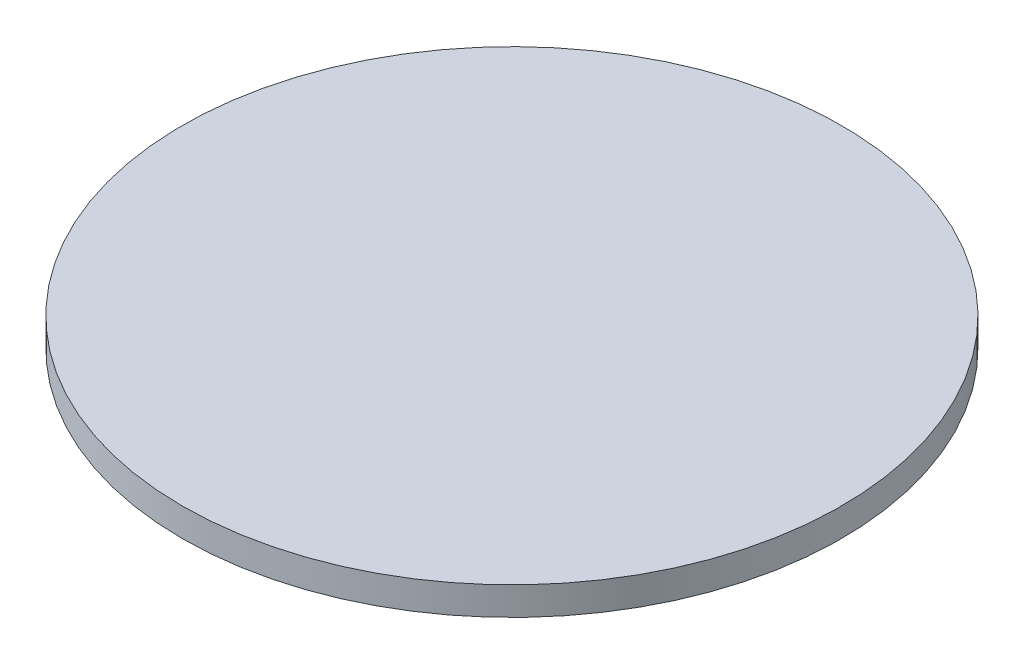
SolidWorks part; units mm, degrees
material "ABS"
ref_plane "Front Plane" through (0, 0, 0) normal (0, 0, 1) x (1, 0, 0)
ref_plane "Top Plane" through (0, 0, 0) normal (0, 1, 0) x (1, 0, 0)
ref_plane "Right Plane" through (0, 0, 0) normal (1, 0, 0) x (0, 0, -1)
sketch "Sketch1" plane through (0, 0, 0) normal (0, 1, 0) x (1, 0, 0)
  circle A0 centre (0, 0) radius 1.55
  dimension "D1" = 3.1
sketch "Sketch3" plane through (0, 0, 0) normal (0, 0, 1) x (1, 0, 0)
  line L0 (0, 0) -> (2.5, 0)
  line L1 (0, 0) -> (0, 5)
  line L2 (0, 5) -> (5, 5)
  line L3 (2.5, 0) -> (5, 5)
  dimension "D1" = 2.5
  dimension "D2" = 5
  dimension "D3" = 5
revolve "Revolve1" add sketch "Sketch3" angle 360 about L1
sketch "Sketch5" plane through (0, 5, 0) normal (0, 1, 0) x (1, 0, 0)
  circle A0 centre (0, 0) radius 5
extrude "Boss-Extrude2" add sketch "Sketch5" along normal blind 5
sketch "Sketch6" plane through (0, 10, 0) normal (0, 1, 0) x (1, 0, 0)
  circle A0 centre (0, 0) radius 17.5
  dimension "D1" = 35
extrude "Boss-Extrude3" add sketch "Sketch6" along normal blind 1.5
sketch "Sketch7" plane through (0, 0, 0) normal (0, -1, 0) x (1, 0, 0)
  circle A0 centre (0, 0) radius 1.7
  dimension "D1" = 3.4
extrude "Cut-Extrude1" cut sketch "Sketch7" against normal blind 7
fillet "Fillet1" radius 10 1 edges at (0, 10, 5)
